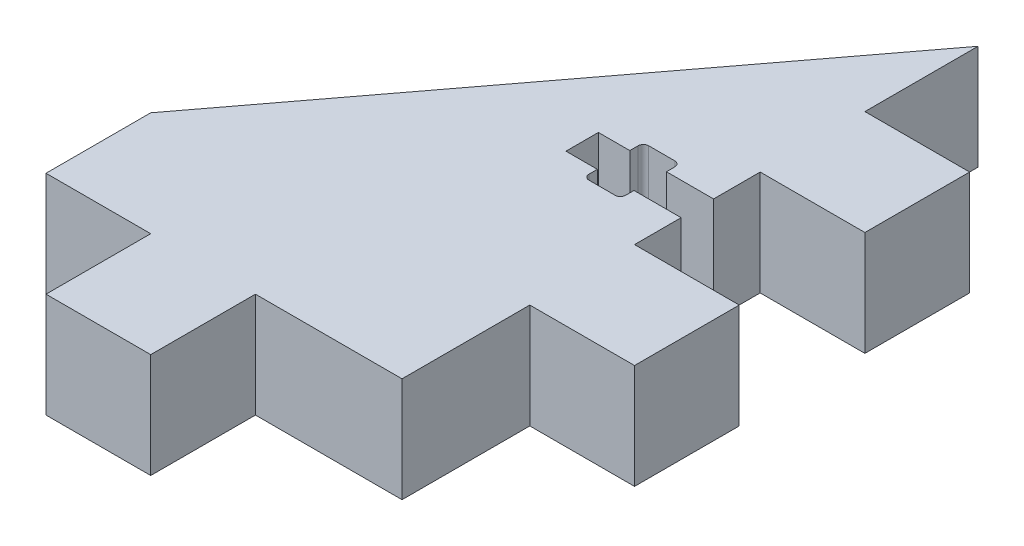
SolidWorks part; units mm, degrees
ref_plane "Front Plane" through (0, 0, 0) normal (0, 0, 1) x (1, 0, 0)
ref_plane "Top Plane" through (0, 0, 0) normal (0, 1, 0) x (1, 0, 0)
ref_plane "Right Plane" through (0, 0, 0) normal (1, 0, 0) x (0, 0, -1)
sketch "Sketch1" plane through (0, 0, 0) normal (0, 1, 0) x (1, 0, 0)
  line L0 (0, 0) -> (-14, 0)
  line L1 (-14, 0) -> (-14, -10)
  line L2 (-14, -10) -> (-24, -10)
  line L3 (-24, -10) -> (-24, 0)
  line L4 (-24, 0) -> (-34, 0)
  line L5 (-34, 0) -> (-34, 10)
  line L6 (-34, 10) -> (0, 55)
  line L7 (0, 55) -> (0, 44.2)
  line L8 (0, 44.2) -> (10, 44.2)
  line L9 (10, 44.2) -> (10, 34.2)
  line L10 (10, 34.2) -> (0, 34.2)
  line L11 (0, 34.2) -> (0, 22.2)
  line L12 (-24, 0) -> (-14, 0) construction
  line L13 (-19, 0) -> (-19, -10) construction
  line L14 (0, 17.2) -> (0, 12.2) construction
  line L15 (5, 12.2) -> (5, 21.2) construction
  line L16 (10, 34.2) -> (10, 22.2) construction
  line L17 (0, 28.2) -> (10, 28.2) construction
  line L24 (0, 22.2) -> (10, 22.2)
  line L25 (10, 22.2) -> (10, 12.2)
  line L26 (10, 12.2) -> (0, 12.2)
  line L27 (0, 12.2) -> (0, 0)
  line L32 (10, 39.2) -> (0, 39.2) construction
  line L33 (0, 39.2) -> (0, 34.2) construction
  line L34 (10, 17.2) -> (0, 17.2) construction
  line L35 (0, 17.2) -> (0, 22.2) construction
  dimension "D1" = 10
  dimension "D2" = 10
  dimension "D3" = 10
  dimension "D7" = 10
  dimension "D8" = 10
  dimension "D10" = 10
  dimension "D11" = 10
  dimension "D12" = 10
  dimension "D9" = 55
  dimension "D4" = 22
  dimension "D6" = 24
  dimension "D5" = 28.2
extrude "Boss-Extrude1" add sketch "Sketch1" along normal blind 10
sketch "Sketch2" [suppressed] plane through (0, 8, 0) normal (0, 1, 0) x (1, 0, 0)
  line L0 (0, 29.9) -> (0, 25.9) construction
  line L1 (0, 27.9) -> (-7.2, 27.9) construction
  line L2 (-7.2, 25.9) -> (-7.2, 29.9) construction
  line L3 (7.5, 36.4) -> (7.5, 20.4) construction
  line L4 (0, 36.4) -> (7.5, 36.4) construction
  line L5 (0, 27.9) -> (7.5, 27.9) construction
sketch "Sketch3" plane through (0, 10, 0) normal (0, 1, 0) x (1, 0, 0)
  line L0 (0, 28.2) -> (-11, 28.2) construction
  line L1 (0, 22.2) -> (0, 34.2) construction
  line L2 (-11, 29.75) -> (-8, 29.75)
  line L3 (-8, 29.75) -> (-8, 30.55)
  line L4 (-7.5, 31.05) -> (-5, 31.05)
  line L5 (-4.5, 30.55) -> (-4.5, 29.75)
  line L6 (-4.5, 29.75) -> (0, 29.75)
  line L7 (0, 29.75) -> (0, 26.65)
  line L8 (-11, 29.75) -> (-11, 26.65)
  line L9 (-4.5, 26.65) -> (0, 26.65)
  line L10 (-4.5, 25.85) -> (-4.5, 26.65)
  line L11 (-7.5, 25.35) -> (-5, 25.35)
  line L12 (-8, 26.65) -> (-8, 25.85)
  line L13 (-11, 26.65) -> (-8, 26.65)
  arc A0 (-8, 30.55) -> (-7.5, 31.05) centre (-7.5, 30.55) cw
  arc A1 (-5, 31.05) -> (-4.5, 30.55) centre (-5, 30.55) cw
  arc A2 (-5, 25.35) -> (-4.5, 25.85) centre (-5, 25.85) ccw
  arc A3 (-8, 25.85) -> (-7.5, 25.35) centre (-7.5, 25.85) ccw
  point P12 (-8, 31.05)
  point P15 (-4.5, 31.05)
  point P26 (-4.5, 25.35)
  point P27 (-8, 25.35)
  dimension "D7" = 0.5
  dimension "D1" = 11
  dimension "D3" = 1.55
  dimension "D2" = 8
  dimension "D4" = 3.5
  dimension "D5" = 2.85
  dimension "D6" = 1.55
extrude "Cut-Extrude1" cut sketch "Sketch3" against normal through all
equation "\"Y-ROD-SPACING\"=75"
equation "\"Y-BED-OFFSET\"=2"
equation "\"Y-BED-ROD-INSET\"=3.5"
equation "\"T-SLOT-NUT-FILLET-RADIUS\"=0.5"
equation "\"T-SLOT-SCREW-SHAFT-RADIUS\"=1.55"
equation "\"T-SLOT-SCREW-SHAFT-CUTOUT-LENGTH\"=11"
equation "\"T-SLOT-NUT-DEPTH\"=3.5"
equation "\"T-SLOT-NUT-WIDTH\"=2.85"
equation "\"T-SLOT-NUT-END-DISTANCE\"=8"
equation "\"ACRYLIC-TAB-CUTOUT-SIZE\"=\"ACRYLIC-THICKNESS\"+\"ACRYLIC-TAB-TOLERANCE\"*2"
equation "\"ACRYLIC-TAB-WIDTH\"=\"ACRYLIC-THICKNESS\""
equation "\"ACRYLIC-M3-HOLE\"=2.9"
equation "\"SMOOTHROD-CAP-SCREW-DISTANCE\"=20"
equation "\"FRAME-WIDTH-INNER\"=370"
equation "\"NEMA17-HOLE-SPACING\"=31"
equation "\"NEMA17-CENTRAL-CUTOUT\"=22.5"
equation "\"D3@Sketch1\"=\"ACRYLIC-TAB-WIDTH\""
equation "\"D12@Sketch1\"=\"ACRYLIC-TAB-WIDTH\""
equation "\"D2@Sketch1\"=\"ACRYLIC-TAB-WIDTH\""
equation "\"D11@Sketch1\"=\"ACRYLIC-TAB-WIDTH\""
equation "\"D1@Sketch1\"=\"ACRYLIC-TAB-WIDTH\""
equation "\"D10@Sketch1\"=\"ACRYLIC-TAB-WIDTH\""
equation "\"Z-BRACKET-REACH\"=55"
equation "\"D9@Sketch1\"=\"Z-BRACKET-REACH\""
equation "\"D6@Sketch3\"=\"T-SLOT-SCREW-SHAFT-RADIUS\""
equation "\"D3@Sketch3\"=\"T-SLOT-SCREW-SHAFT-RADIUS\""
equation "\"D4@Sketch3\"=\"T-SLOT-NUT-DEPTH\""
equation "\"D7@Sketch3\"=\"T-SLOT-NUT-FILLET-RADIUS\""
equation "\"D1@Sketch3\"=\"T-SLOT-SCREW-SHAFT-CUTOUT-LENGTH\""
equation "\"D5@Sketch3\"=\"T-SLOT-NUT-WIDTH\""
equation "\"D2@Sketch3\"=\"T-SLOT-NUT-END-DISTANCE\""
equation "\"X-ROD-SPACING\"=45"
equation "\"Z-ROD-SPACING\"=17.5"
equation "\"ACRYLIC-THICKNESS\"=10"
equation "\"ACRYLIC-THICKNESS2\"=4.5"
equation "\"TOP-BRACKET-SPACING\"=40"
equation "\"SMOOTHROD-X-LENGTH\"=350"
equation "\"SMOOTHROD-Y-LENGTH\"=350"
equation "\"SMOOTHROD-Z-LENGTH\"=350"
equation "\"SMOOTHROD-TIGHTENING-HEADROOM\"=.25"
equation "\"LEADSCREW-Z-LENGTH\"=300"
equation "\"SCREW-LENGTH-FRAME\"=\"ACRYLIC-THICKNESS\" + 10"
equation "\"SCREW-HEAD-RADIUS\"=6"
equation "\"PRINTED-X-SMOOTHROD-DIAMETER\"=9.0"
equation "\"PRINTED-X-SMOOTHROD-CUTOUT\"=10"
equation "\"PRINTED-X-BASE-HEIGHT\"=10"
equation "\"PRINTED-LM8UU-CUTOUT-SIZE\"=15.5"
equation "\"PRINTED-LM8UU-CUTOUT-LENGTH\"=24.5"
equation "\"PRINTED-X-IDLER-HEIGHT\"=16"
equation "\"PSU-MOUNTING-WIDTH\"=95"
equation "\"PSU-MOUNTING-HEIGHT\"=177"
equation "\"D1@Boss-Extrude1\"=\"ACRYLIC-THICKNESS\""
